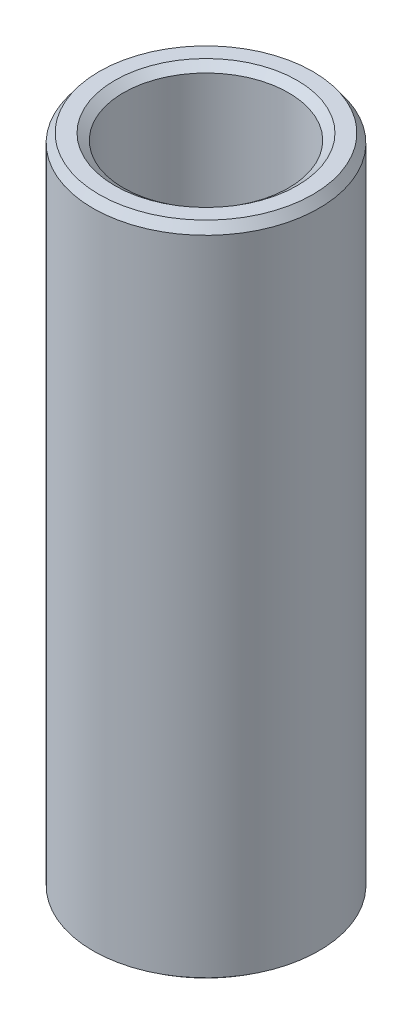
SolidWorks part; units mm, degrees
ref_plane "Front Plane" through (0, 0, 0) normal (0, 0, 1) x (1, 0, 0)
ref_plane "Top Plane" through (0, 0, 0) normal (0, 1, 0) x (1, 0, 0)
ref_plane "Right Plane" through (0, 0, 0) normal (1, 0, 0) x (0, 0, -1)
sketch "Sketch1" plane through (0, 0, 0) normal (0, 1, 0) x (1, 0, 0)
  circle A0 centre (0, 0) radius 50
  dimension "SLEEVE_OD" = 100
extrude "Boss-Extrude1" add sketch "Sketch1" along normal blind 290.9875
sketch "Sketch2" plane through (0, 0, 0) normal (0, 1, 0) x (1, 0, 0)
  circle A0 centre (0, 0) radius 36.5025
  dimension "BORE_D" = 73.0049
extrude "Cut-Extrude1" cut sketch "Sketch2" along normal through all
chamfer "Chamfer1" distance 3.8354 angle 36.291 4 edges at (0, 290.9875, 36.5025) (0, 0, 36.5025) (0, 0, 50) (0, 290.9875, 50) first distance on face at (0, 290.9875, 36.5025) first distance on face at (0, 0, 36.5025) first distance on face at (0, 290.9875, 50)
